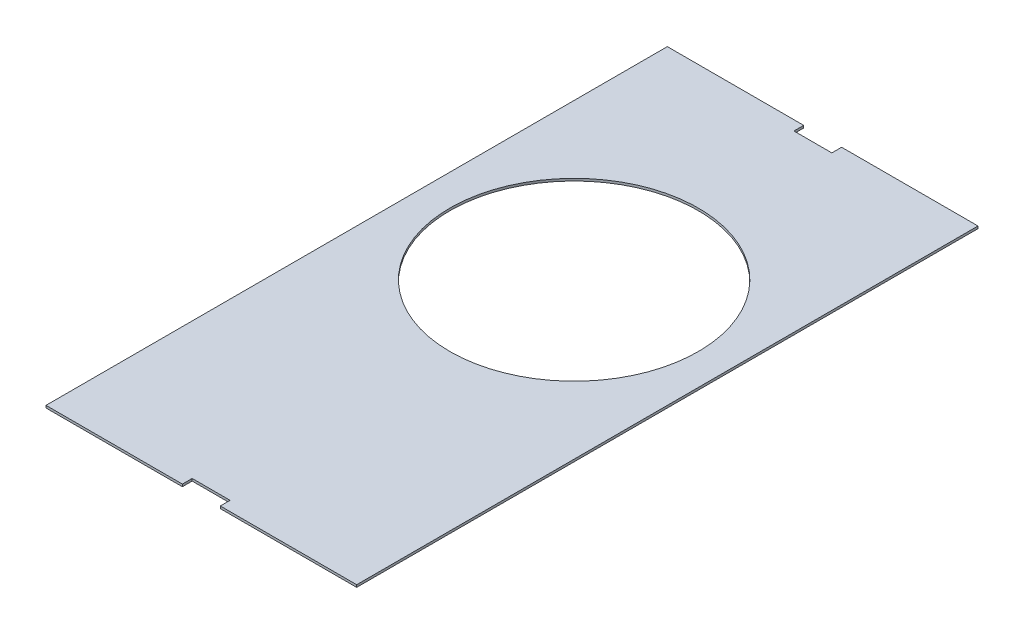
SolidWorks part; units mm, degrees
ref_plane "Front Plane" through (0, 0, 0) normal (0, 0, 1) x (1, 0, 0)
ref_plane "Top Plane" through (0, 0, 0) normal (0, 1, 0) x (1, 0, 0)
ref_plane "Right Plane" through (0, 0, 0) normal (1, 0, 0) x (0, 0, -1)
sketch "BaseSketch" plane through (0, 0, 0) normal (0, 1, 0) x (1, 0, 0)
  line L1 (-254, -508) -> (254, -508)
  line L2 (-254, -508) -> (-254, 508)
  line L3 (-254, 508) -> (254, 508)
  line L4 (254, -508) -> (254, 508)
  line L5 (-254, -508) -> (254, 508) construction
  line L6 (-254, 508) -> (254, -508) construction
  point P0 (0, 0)
extrude "Boss-Extrude1" add sketch "BaseSketch" along normal blind 3.81
sketch "TabCutSketch" plane through (0, 3.81, 0) normal (0, 1, 0) x (1, 0, 0)
  line L0 (-254, -508) -> (254, -508) construction
  line L1 (-31, -508) -> (31, -508)
  line L2 (-31, -508) -> (-31, -492)
  line L3 (-31, -492) -> (31, -492)
  line L4 (31, -508) -> (31, -492)
  line L10 (0, 0) -> (0, 492) construction
  line L11 (0, 492) -> (0, 0) construction
  line L12 (254, 508) -> (-254, 508) construction
  line L13 (31, 508) -> (-31, 508)
  line L14 (31, 508) -> (31, 492)
  line L15 (31, 492) -> (-31, 492)
  line L16 (-31, 508) -> (-31, 492)
  line L17 (0, 0) -> (0, -492) construction
  point P0 (0, -508)
  dimension "D1" = 16
  dimension "D2" = 62
  dimension "D3" = 16
  dimension "D4" = 62
extrude "Cut-Extrude1" cut sketch "TabCutSketch" against normal through all
sketch "Sketch6" plane through (0, 3.81, 0) normal (0, 1, 0) x (1, 0, 0)
  line L1 (254, 508) -> (31, 508) construction
  circle A0 centre (0, 101.6) radius 203.2
  dimension "D2" = 406.4
  dimension "D1" = 406.4
extrude "Cut-Extrude10" cut sketch "Sketch6" against normal blind 3.81
